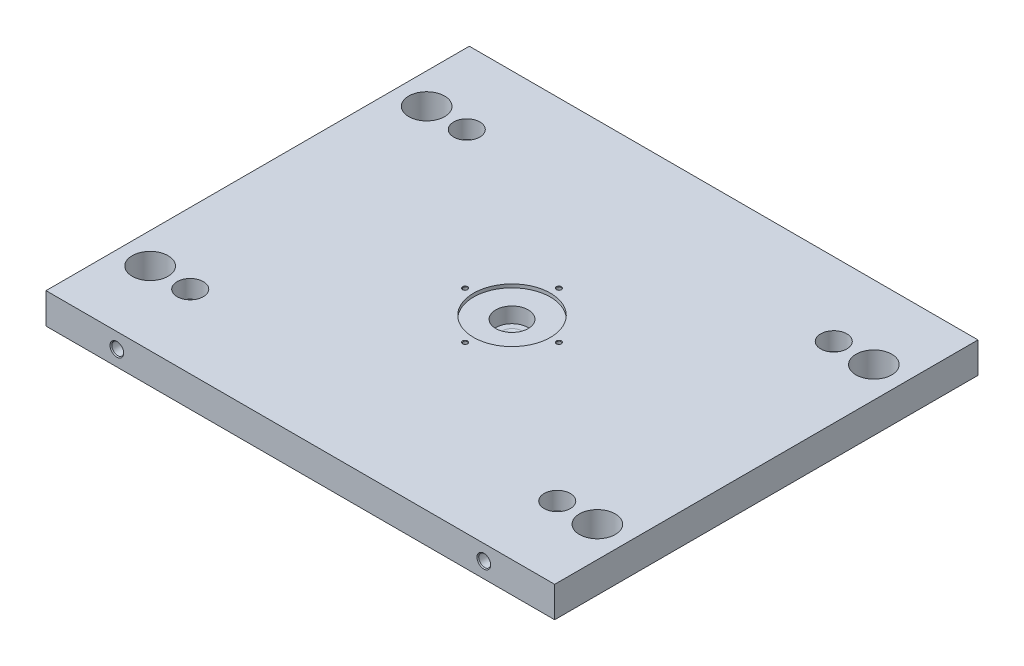
SolidWorks part; units mm, degrees
material "1.2312 (40CrMnMoS8-6)"
ref_plane "Płaszczyzna przednia" through (0, 0, 0) normal (0, 0, 1) x (1, 0, 0)
ref_plane "Płaszczyzna górna" through (0, 0, 0) normal (0, 1, 0) x (1, 0, 0)
ref_plane "Płaszczyzna prawa" through (0, 0, 0) normal (1, 0, 0) x (0, 0, -1)
sketch "Szkic1" plane through (0, 0, 0) normal (0, 1, 0) x (1, 0, 0)
  line L0 (298, 496) -> (298, 0) construction
  line L1 (0, 496) -> (596, 496)
  line L2 (0, 496) -> (0, 0)
  line L3 (0, 0) -> (596, 0)
  line L4 (596, 496) -> (596, 0)
  line L5 (0, 248) -> (596, 248) construction
  circle A0 centre (36, 410) radius 21
  circle A1 centre (560, 410) radius 21
  circle A2 centre (560, 86) radius 21
  circle A3 centre (36, 86) radius 21
  circle A4 centre (298, 248) radius 45
  dimension "D3" = 524
  dimension "D4" = 324
  dimension "D1" = 596
  dimension "D2" = 496
extrude "Dodanie-wyciągnięcie1" add sketch "Szkic1" against normal blind 36 contours A4 | L4 L1 L2 L3 A4 A1 A0 A2 A3 region at (298, 0, -488.2461) region at (298, 0, -248)
sketch "Szkic6" plane through (0, 0, 0) normal (0, 1, 0) x (1, 0, 0)
  line L1 (83, 410) -> (513, 410)
  line L2 (83, 410) -> (83, 86)
  line L3 (83, 86) -> (513, 86)
  line L4 (513, 410) -> (513, 86)
  line L5 (298, 496) -> (298, 0) construction
  line L6 (0, 248) -> (596, 248) construction
  dimension "D1" = 430
  dimension "D2" = 324
  dimension "D3" = 215
  dimension "D4" = 162
extrude "Wytnij-wyciągnięcie1" cut sketch "Szkic1<5>" against normal blind 4 contours A4 region at (298, 0, -248)
sketch "Szkic1<5>" plane through (0, 0, 0) normal (0, 1, 0) x (1, 0, 0) same geometry as "Szkic1"
hole_wizard "Pogłębienie walcowe pod M16 Wkręt z łbem sześciokątnym z gniazdem2" positions "Szkic 3D5" profile "Szkic7" counterbore size "M16" standard "ISO" end condition through all
sketch3d "Szkic 3D5"
  point P0 (83, 0, -410)
  point P3 (513, 0, -410)
  point P6 (513, 0, -86)
  point P9 (83, 0, -86)
sketch "Szkic7" plane through (83, 0, -410) normal (1, 0, 0) x (0, 0, 1)
  line L0 (0, 0) -> (0, 36)
  line L1 (0, 36) -> (8.75, 36)
  line L3 (8.75, 36) -> (8.75, 21)
  line L4 (8.75, 21) -> (15.3565, 21)
  line L5 (15.3565, 21) -> (15.3565, 0)
  line L7 (15.3565, 0) -> (0, 0)
  line L11 (0, -6.35) -> (0, 107.95) construction
  dimension "Średnica otworu na wylot" = 17.5
  dimension "Głębokość otworu na wylot" = 36
  dimension "Średnica pogłębienia walcowego" = 30.713
  dimension "Głębokość pogłębienia walcowego" = 21
sketch "Szkic8" plane through (0, -4, 0) normal (0, 1, 0) x (1, 0, 0)
  line L0 (298, 496) -> (298, 0) construction
  circle A0 centre (298, 248) radius 19
  circle A1 centre (298, 248) radius 9
extrude "Wytnij-wyciągnięcie2" cut sketch "Szkic8" against normal through all contours A1 region at (298, -4, -248)
extrude "Wytnij-wyciągnięcie3" cut sketch "Szkic8<3>" against normal blind 18
sketch "Szkic8<3>" plane through (0, -4, 0) normal (0, 1, 0) x (1, 0, 0) same geometry as "Szkic8"
fillet "Zaokrąglenie1" radius 3 1 edges at (298, -22, -239)
sketch "Szkic9" plane through (0, -22, 0) normal (0, 1, 0) x (1, 0, 0)
  line L0 (298, 248) -> (313, 248) construction
  point P3 (313, 248)
hole_wizard "Otwory ustalające Ø4.0mm1" positions "Szkic 3D6" profile "Szkic10" hole size "Ø4.0" standard "ISO"
sketch3d "Szkic 3D6"
  point P0 (313, -22, -248)
sketch "Szkic10" plane through (313, -22, -248) normal (1, 0, 0) x (0, 0, 1)
  line L0 (0, 0) -> (0, 6.2017)
  line L1 (0, 6.2017) -> (2, 5)
  line L2 (2, 5) -> (2, 0)
  line L5 (2, 0) -> (0, 0)
  line L10 (0, 6.2017) -> (-2, 5) construction
  line L11 (0, -6.35) -> (0, 107.95) construction
  dimension "Średnica otworu" = 4
  dimension "Głębokość otworu" = 5
  dimension "Kąt wiertła" = 118
sketch "Szkic11" plane through (0, 0, 0) normal (0, 1, 0) x (1, 0, 0)
  circle A0 centre (298, 248) radius 55
  point P3 (298, 303)
  point P4 (298, 193)
  point P5 (243, 248)
  point P6 (353, 248)
hole_wizard "Otwór gwintowany M61" positions "Szkic 3D7" profile "Szkic12" tap size "M6" standard "ISO"
sketch3d "Szkic 3D7"
  point P0 (243, 0, -248)
  point P3 (298, 0, -303)
  point P6 (353, 0, -248)
  point P9 (298, 0, -193)
sketch "Szkic12" plane through (243, 0, -248) normal (1, 0, 0) x (0, 0, 1)
  line L0 (0, 0) -> (0, 18.5022)
  line L1 (0, 18.5022) -> (2.5, 17)
  line L2 (2.5, 17) -> (2.5, 0.525)
  line L3 (2.5, 0.525) -> (3.025, 0)
  line L5 (3.025, 0) -> (0, 0)
  line L6 (-2.5, 0.525) -> (-3.025, 0) construction
  line L10 (0, 18.5022) -> (-2.5, 17) construction
  line L11 (0, -6.35) -> (0, 107.95) construction
  dimension "Średnica wiertła gwintu" = 5
  dimension "Głębokość otworu gwintowanego" = 17
  dimension "Średnica zewnętrznego pogłębienia stożkowego" = 6.05
  dimension "Kąt zewnętrznego pogłębienia stożkowego" = 90
  dimension "Kąt wiertła" = 118
cosmetic thread "Gwint otworu1" parameters "D1"=12, "D2"=6
cosmetic thread "Gwint otworu2" parameters "D1"=12, "D2"=6
cosmetic thread "Gwint otworu3" parameters "D1"=12, "D2"=6
cosmetic thread "Gwint otworu4" parameters "D1"=12, "D2"=6
sketch "Szkic13" plane through (0, 0, 0) normal (0, 0, 1) x (1, 0, 0)
  line L0 (0, -18) -> (596, -18) construction
  line L1 (0, -36) -> (0, 0) construction
  line L2 (596, -36) -> (596, 0) construction
  line L3 (298, 0) -> (298, -36) construction
  line L4 (0, 0) -> (596, 0) construction
  line L5 (0, -36) -> (596, -36) construction
  point P12 (83, -18)
  point P13 (513, -18)
  dimension "D1" = 430
hole_wizard "Otwór gwintowany M161" positions "Szkic 3D8" profile "Szkic14" tap size "M16" standard "ISO"
sketch3d "Szkic 3D8"
  point P0 (83, -18, 0)
  point P3 (513, -18, 0)
sketch "Szkic14" plane through (83, -18, 0) normal (1, 0, 0) x (0, -1, 0)
  line L0 (0, 0) -> (0, 46.206)
  line L1 (0, 46.206) -> (7, 42)
  line L2 (7, 42) -> (7, 1.025)
  line L3 (7, 1.025) -> (8.025, 0)
  line L5 (8.025, 0) -> (0, 0)
  line L6 (-7, 1.025) -> (-8.025, 0) construction
  line L10 (0, 46.206) -> (-7, 42) construction
  line L11 (0, -6.35) -> (0, 107.95) construction
  dimension "Średnica wiertła gwintu" = 14
  dimension "Głębokość otworu gwintowanego" = 42
  dimension "Średnica zewnętrznego pogłębienia stożkowego" = 16.05
  dimension "Kąt zewnętrznego pogłębienia stożkowego" = 90
  dimension "Kąt wiertła" = 118
cosmetic thread "Gwint otworu5" parameters "D1"=32, "D2"=16
cosmetic thread "Gwint otworu6" parameters "D1"=32, "D2"=16
